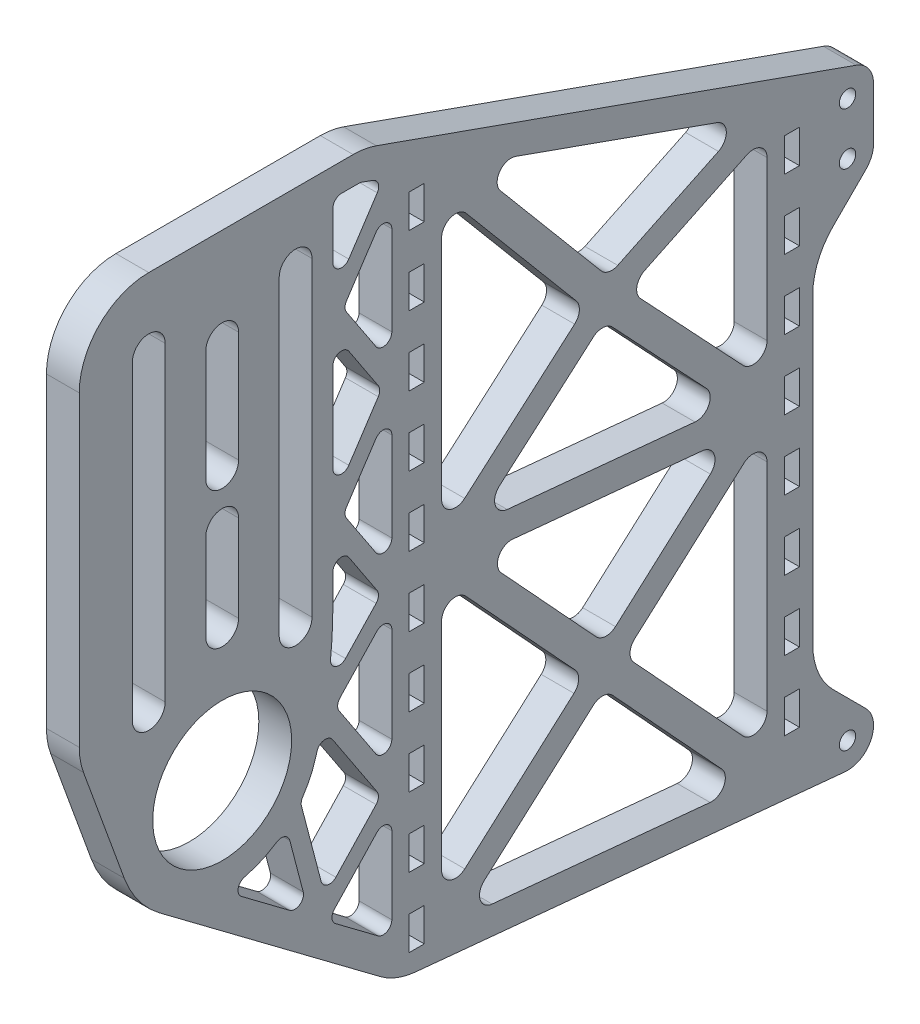
SolidWorks part; units mm, degrees
ref_plane "Front Plane" through (0, 0, 0) normal (0, 0, 1) x (1, 0, 0)
ref_plane "Top Plane" through (0, 0, 0) normal (0, 1, 0) x (1, 0, 0)
ref_plane "Right Plane" through (0, 0, 0) normal (1, 0, 0) x (0, 0, -1)
sketch "PlateGeometry" plane through (0, 0, 0) normal (1, 0, 0) x (0, 0, -1)
  line L1 (-38.1, -76.2) -> (38.1, -76.2) construction
  line L2 (-38.1, -76.2) -> (-38.1, 76.2) construction
  line L3 (-38.1, 76.2) -> (38.1, 76.2) construction
  line L4 (38.1, -76.2) -> (38.1, 76.2) construction
  line L5 (-38.1, -76.2) -> (38.1, 76.2) construction
  line L6 (-38.1, 76.2) -> (38.1, -76.2) construction
  line L11 (31.75, 76.2) -> (-31.75, 76.2) construction
  line L12 (31.75, 76.2) -> (31.75, -76.2) construction
  line L13 (31.75, -76.2) -> (-31.75, -76.2) construction
  line L14 (-31.75, 76.2) -> (-31.75, -76.2) construction
  line L15 (31.75, 76.2) -> (-31.75, -76.2) construction
  line L16 (31.75, -76.2) -> (-31.75, 76.2) construction
  point P0 (0, 0)
  point P9 (0, 0)
  line B0 (-35.7923, -66.6761) -> (-32.7923, -66.6739)
  line B1 (-35.7923, -66.6761) -> (-35.7877, -73.0261)
  line B2 (-35.7877, -73.0261) -> (-32.7877, -73.0239)
  line B3 (-32.7923, -66.6739) -> (-32.7877, -73.0239)
  line B4 (-35.7923, -66.6761) -> (-32.7877, -73.0239) construction
  line B5 (-35.7877, -73.0261) -> (-32.7923, -66.6739) construction
  line B6 (-35.7923, -53.9761) -> (-32.7923, -53.9739)
  line B7 (-35.7923, -53.9761) -> (-35.7877, -60.3261)
  line B8 (-35.7877, -60.3261) -> (-32.7877, -60.3239)
  line B9 (-32.7923, -53.9739) -> (-32.7877, -60.3239)
  line B10 (-35.7923, -53.9761) -> (-32.7877, -60.3239) construction
  line B11 (-35.7877, -60.3261) -> (-32.7923, -53.9739) construction
  line B12 (-35.7923, -41.2761) -> (-32.7923, -41.2739)
  line B13 (-35.7923, -41.2761) -> (-35.7877, -47.6261)
  line B14 (-35.7877, -47.6261) -> (-32.7877, -47.6239)
  line B15 (-32.7923, -41.2739) -> (-32.7877, -47.6239)
  line B16 (-35.7923, -41.2761) -> (-32.7877, -47.6239) construction
  line B17 (-35.7877, -47.6261) -> (-32.7923, -41.2739) construction
  line B18 (-35.7877, -34.9261) -> (-32.7877, -34.9239)
  line B19 (-32.7923, -28.5739) -> (-32.7877, -34.9239)
  line B20 (-35.7923, -15.8761) -> (-35.7877, -22.2261)
  line B21 (-35.7877, -22.2261) -> (-32.7877, -22.2239)
  line B22 (-32.7923, -15.8739) -> (-32.7877, -22.2239)
  line B23 (-35.7923, 9.5239) -> (-32.7923, 9.5261)
  line B24 (-32.7923, 9.5261) -> (-32.7877, 3.1761)
  line B25 (-35.7923, 9.5239) -> (-32.7877, 3.1761) construction
  line B26 (-35.7923, 22.2239) -> (-35.7877, 15.8739)
  line B27 (-35.7923, 34.9239) -> (-35.7877, 28.5739)
  line B28 (-35.7923, 47.6239) -> (-35.7877, 41.2739)
  line B29 (-35.7877, 41.2739) -> (-32.7923, 47.6261) construction
  line B30 (32.7886, -66.6757) -> (32.7914, -73.0257)
  line B31 (32.7914, -73.0257) -> (35.7914, -73.0243)
  line B32 (35.7886, -66.6743) -> (35.7914, -73.0243)
  line B33 (32.7886, -66.6757) -> (35.7914, -73.0243) construction
  line B34 (32.7914, -73.0257) -> (35.7886, -66.6743) construction
  line B35 (32.7886, -53.9757) -> (32.7914, -60.3257)
  line B36 (32.7914, -60.3257) -> (35.7914, -60.3243)
  line B37 (35.7886, -53.9743) -> (35.7914, -60.3243)
  line B38 (32.7886, -53.9757) -> (35.7914, -60.3243) construction
  line B39 (32.7914, -60.3257) -> (35.7886, -53.9743) construction
  line B40 (35.7886, -41.2743) -> (35.7914, -47.6243)
  line B41 (32.7914, -34.9257) -> (35.7914, -34.9243)
  line B42 (32.7886, -28.5757) -> (35.7914, -34.9243) construction
  line B43 (32.7886, -15.8757) -> (32.7914, -22.2257)
  line B44 (32.7886, -3.1757) -> (35.7914, -9.5243) construction
  line B45 (32.7914, -9.5257) -> (35.7886, -3.1743) construction
  line B46 (32.7886, 9.5243) -> (35.7886, 9.5257)
  line B47 (32.7886, 9.5243) -> (32.7914, 3.1743)
  line B48 (32.7914, 3.1743) -> (35.7914, 3.1757)
  line B49 (32.7886, 9.5243) -> (35.7914, 3.1757) construction
  line B50 (32.7886, 22.2243) -> (32.7914, 15.8743)
  line B51 (35.7886, 22.2257) -> (35.7914, 15.8757)
  line B52 (32.7886, 22.2243) -> (35.7914, 15.8757) construction
  line B53 (32.7914, 15.8743) -> (35.7886, 22.2257) construction
  line B54 (32.7914, 41.2743) -> (35.7914, 41.2757)
  line B55 (35.7886, 47.6257) -> (35.7914, 41.2757)
  line B56 (32.7886, 60.3243) -> (32.7914, 53.9743)
  line B57 (35.7886, 60.3257) -> (35.7914, 53.9757)
  line B58 (32.7886, 73.0243) -> (32.7914, 66.6743)
  line B59 (35.7886, 73.0257) -> (35.7914, 66.6757)
  line B60 (32.7914, 66.6743) -> (35.7886, 73.0257) construction
  circle B61 centre (-37.3063, -73.025) radius 5.5563 construction
  circle B62 centre (-37.3063, -73.025) radius 6.8263 construction
  circle B63 centre (-44.9262, -53.975) radius 5.5563 construction
  circle B64 centre (-44.9262, -53.975) radius 6.8263 construction
  dimension "D11" = 63.5
  dimension "D12" = 3.175
  dimension "D1" = 76.2
  dimension "D2" = 152.4
  dimension "D4" = 3.81
  dimension "D5" = 6.35
  dimension "D6" = 12.7
  dimension "D7" = 6.35
  dimension "D8" = 3.81
  dimension "D10" = 12.7
  dimension "D13" = 19.05
  dimension "D14" = 7.62
  dimension "D3" = 12
  dimension "D9" = 12
sketch_block_instance "SlotOutline-1"
sketch_block "SlotOutline" parameters "D1"=18.06, "D2"=7.2935
sketch_block_instance "SlotOutline-2"
sketch_block_instance "SlotOutline-3"
sketch_block_instance "SlotOutline-4"
sketch_block_instance "SlotOutline-5"
sketch_block_instance "SlotOutline-6"
sketch_block_instance "SlotOutline-7"
sketch_block_instance "SlotOutline-8"
sketch_block_instance "SlotOutline-9"
sketch_block_instance "SlotOutline-10"
sketch_block_instance "SlotOutline-11"
sketch_block_instance "SlotOutline-12"
sketch_block_instance "SlotOutline-13"
sketch_block_instance "SlotOutline-14"
sketch_block_instance "SlotOutline-15"
sketch_block_instance "SlotOutline-16"
sketch_block_instance "SlotOutline-17"
sketch_block_instance "SlotOutline-18"
sketch_block_instance "SlotOutline-19"
sketch_block_instance "SlotOutline-20"
sketch_block_instance "SlotOutline-21"
sketch_block_instance "SlotOutline-22"
sketch_block_instance "SlotOutline-23"
sketch_block_instance "SlotOutline-24"
sketch_block_instance "PulleyOutline-1"
sketch_block "PulleyOutline" parameters "D1"=11.1125, "D2"=13.6525
sketch_block_instance "PulleyOutline-2"
sketch "MotorGeometry" plane through (0, 0, 0) normal (1, 0, 0) x (0, 0, -1)
  line L0 (-83.2734, 1.775) -> (-83.2734, 49.025) construction
  line L3 (-50.2786, -55.4665) -> (-63.8121, -13.9087) construction
  line L4 (-41.2645, -76.9242) -> (-75.3216, -19.0975) construction
  line L5 (-38.1, -76.2) -> (-38.1, 76.2) construction
  line L6 (-38.1, -76.2) -> (38.1, -76.2) construction
  line L7 (38.1, -76.2) -> (38.1, 76.2) construction
  line L8 (-83.2734, 17.65) -> (-69.85, 9.9) construction
  line L9 (-69.85, 9.9) -> (-56.4266, 17.65) construction
  line L10 (-56.4266, 17.65) -> (-56.4266, 33.15) construction
  line L11 (-56.4266, 33.15) -> (-69.85, 40.9) construction
  line L12 (-69.85, 40.9) -> (-83.2734, 33.15) construction
  line L13 (-83.2734, 33.15) -> (-83.2734, 17.65) construction
  line L14 (-86.2734, 1.775) -> (-86.2734, 49.025)
  line L15 (-80.2734, 1.775) -> (-80.2734, 49.025)
  line L16 (-56.4266, 1.775) -> (-56.4266, 49.025) construction
  line L17 (-59.4266, 1.775) -> (-59.4266, 49.025)
  line L18 (-53.4266, 1.775) -> (-53.4266, 49.025)
  line L19 (-69.85, 8.3125) -> (-69.85, 47.25) construction
  line L20 (-72.85, 8.3125) -> (-72.85, 47.25)
  line L21 (-66.85, 8.3125) -> (-66.85, 47.25)
  circle A0 centre (44.45, -66.675) radius 1.5
  circle A1 centre (-69.85, -15.875) radius 11
  circle A5 centre (-69.85, -15.875) radius 30 construction
  circle A6 centre (-69.85, -15.875) radius 6.35 construction
  circle A7 centre (-44.9262, -53.975) radius 5.5562 construction
  circle A8 centre (-37.3063, -73.025) radius 5.5562 construction
  circle A9 centre (-69.85, -15.875) radius 25.5 construction
  circle A10 centre (-69.85, 25.4) radius 16 construction
  circle A11 centre (-69.85, 25.4) radius 11.5 construction
  circle A12 centre (-69.85, 25.4) radius 13.4234 construction
  arc A13 (-86.2734, 1.775) -> (-80.2734, 1.775) centre (-83.2734, 1.775) ccw
  arc A14 (-80.2734, 49.025) -> (-86.2734, 49.025) centre (-83.2734, 49.025) ccw
  arc A15 (-59.4266, 1.775) -> (-53.4266, 1.775) centre (-56.4266, 1.775) ccw
  arc A16 (-53.4266, 49.025) -> (-59.4266, 49.025) centre (-56.4266, 49.025) ccw
  arc A17 (-72.85, 8.3125) -> (-66.85, 8.3125) centre (-69.85, 8.3125) ccw
  arc A18 (-66.85, 47.25) -> (-72.85, 47.25) centre (-69.85, 47.25) ccw
  point P29 (-83.2734, 25.4)
  point P39 (-56.4266, 25.4)
  point P46 (-69.85, 27.7812)
  dimension "D1" = 22
  dimension "D4" = 60
  dimension "D5" = 12.7
  dimension "D7" = 4.5
  dimension "D8" = 32
  dimension "D9" = 4.5
  dimension "D13" = 3
  dimension "D3" = 6
  dimension "D2" = 31
  dimension "D6" = 38.1
  dimension "D10" = 31.75
  dimension "D11" = 9.525
  dimension "D12" = 6.35
  dimension "D14" = 15.875
  dimension "D15" = 1.5875
  dimension "D16" = 15.875
  dimension "D17" = 6.35
  dimension "D18" = 41.275
sketch "Sketch4" plane through (0, 0, 0) normal (1, 0, 0) x (0, 0, -1)
  line L0 (49.2125, 25.4) -> (49.2125, 34.925)
  line L1 (47.8176, 22.0324) -> (38.1, 12.3148)
  line L2 (-30.48, -50.8) -> (-38.1, -50.8) construction
  line L3 (-30.48, -50.8) -> (-30.48, -63.5) construction
  line L4 (-30.48, -63.5) -> (-38.1, -63.5) construction
  line L5 (-38.1, -50.8) -> (-38.1, -63.5) construction
  line L6 (-30.48, -50.8) -> (-38.1, -63.5) construction
  line L7 (-30.48, -63.5) -> (-38.1, -50.8) construction
  line L8 (38.1, 12.3148) -> (38.1, -53.5898)
  line L9 (38.1, -53.5898) -> (47.8176, -63.3074)
  line L10 (38.1, -76.2) -> (38.1, 76.2) construction
  line L11 (43.9929, -71.4155) -> (-38.1, -63.5)
  line L12 (-38.1, -63.5) -> (-81.28, -31.115)
  line L13 (-87.7511, -22.3905) -> (-95.9734, 0.2)
  line L14 (-95.9734, 0.2) -> (-95.9734, 71.25)
  line L15 (-43.7266, 71.25) -> (46.0419, 39.4136)
  line L16 (-95.9734, 71.25) -> (-43.7266, 71.25)
  line L17 (-83.2734, 1.775) -> (-83.2734, 58.55) construction
  line L18 (-86.2734, 1.775) -> (-86.2734, 58.55)
  line L19 (-80.2734, 1.775) -> (-80.2734, 58.55)
  line L20 (-69.85, 8.3125) -> (-69.85, 53.6) construction
  line L21 (-72.85, 8.3125) -> (-72.85, 53.6)
  line L22 (-66.85, 8.3125) -> (-66.85, 53.6)
  line L23 (-56.4266, 1.775) -> (-56.4266, 58.55) construction
  line L24 (-59.4266, 1.775) -> (-59.4266, 58.55)
  line L25 (-53.4266, 1.775) -> (-53.4266, 58.55)
  circle A0 centre (44.45, 25.4) radius 1.5
  circle A1 centre (44.45, 34.925) radius 1.5
  circle A2 centre (44.45, -66.675) radius 4.7625 construction
  circle A3 centre (44.45, 25.4) radius 4.7625 construction
  circle A4 centre (44.45, 34.925) radius 4.7625 construction
  circle A5 centre (-69.85, -15.875) radius 12.7
  arc A6 (43.9929, -71.4155) -> (47.8176, -63.3074) centre (44.45, -66.675) ccw
  circle A7 centre (-69.85, -15.875) radius 19.05
  arc A8 (47.8176, 22.0324) -> (49.2125, 25.4) centre (44.45, 25.4) ccw
  arc A9 (49.2125, 34.925) -> (46.0419, 39.4136) centre (44.45, 34.925) ccw
  circle A10 centre (44.45, -66.675) radius 1.5
  arc A11 (-86.2734, 1.775) -> (-80.2734, 1.775) centre (-83.2734, 1.775) ccw
  arc A12 (-80.2734, 58.55) -> (-86.2734, 58.55) centre (-83.2734, 58.55) ccw
  arc A13 (-72.85, 8.3125) -> (-66.85, 8.3125) centre (-69.85, 8.3125) ccw
  arc A14 (-66.85, 53.6) -> (-72.85, 53.6) centre (-69.85, 53.6) ccw
  arc A15 (-59.4266, 1.775) -> (-53.4266, 1.775) centre (-56.4266, 1.775) ccw
  arc A16 (-53.4266, 58.55) -> (-59.4266, 58.55) centre (-56.4266, 58.55) ccw
  arc A17 (-72.85, 24.1875) -> (-66.85, 24.1875) centre (-69.85, 24.1875) cw
  arc A18 (-72.85, 33.3625) -> (-66.85, 33.3625) centre (-69.85, 33.3625) ccw
  point P12 (-34.29, -57.15)
  point P36 (-83.2734, 30.1625)
  point P47 (-69.85, 30.9562)
  point P55 (-56.4266, 30.1625)
  dimension "D1" = 3
  dimension "D4" = 9.525
  dimension "D9" = 25.4
  dimension "D10" = 38.1
  dimension "D11" = 6
  dimension "D14" = 3.175
  dimension "D2" = 9.525
  dimension "D3" = 101.6
  dimension "D5" = 3.81
  dimension "D6" = 12.7
  dimension "D7" = 45
  dimension "D8" = 45
  dimension "D12" = 12.7
  dimension "D13" = 25.4
  dimension "D15" = 15.875
  dimension "D16" = 12.7
  dimension "D17" = 12.7
  dimension "D18" = 20
  dimension "D19" = 12.7
extrude "Boss-Extrude1" add sketch "Sketch4" along normal mid plane 6 contours L0 A9 L13 A7 L12 L11 A6 L9 L8 L1 A8 A0 A1 | A7 A5 | A18 L21 A17 L22 region at (0, 1.9375, 18.512) region at (0, 2.355, 73.0644) region at (0, 28.775, 69.85)
sketch "Sketch5" plane through (3, 0, 0) normal (1, 0, 0) x (0, 0, -1)
  line B0 (35.665, -54.102) -> (32.915, -54.102)
  line B1 (35.665, -54.102) -> (35.665, -60.198)
  line B2 (35.665, -60.198) -> (32.915, -60.198)
  line B3 (32.915, -54.102) -> (32.915, -60.198)
  line B4 (35.665, -54.102) -> (32.915, -60.198) construction
  line B5 (35.665, -60.198) -> (32.915, -54.102) construction
  line B6 (-32.915, -54.102) -> (-35.665, -54.102)
  line B7 (-32.915, -54.102) -> (-32.915, -60.198)
  line B8 (-32.915, -60.198) -> (-35.665, -60.198)
  line B9 (-35.665, -54.102) -> (-35.665, -60.198)
  line B10 (-32.915, -54.102) -> (-35.665, -60.198) construction
  line B11 (-32.915, -60.198) -> (-35.665, -54.102) construction
sketch_block_instance "Slot-1"
sketch_block "Slot" parameters "D1"=11.2845, "D2"=5.6739
sketch_block_instance "Slot-2"
extrude "LowerSlot" cut sketch "Sketch5" against normal through all both and the other way through all contours B0 B3 B2 B1 region at (3, -57.15, -34.29)
extrude "UpperSlot" cut sketch "Sketch5<3>" against normal through all both and the other way through all contours B6 B9 B8 B7 region at (3, -57.15, 34.29)
sketch "Sketch5<3>" plane through (3, 0, 0) normal (1, 0, 0) x (0, 0, -1) same geometry as "Sketch5"
pattern_linear "LowerSlots" count 8 spacing 12.7 along (0, 1, 0) of "LowerSlot"
pattern_linear "LPattern2" count 10 spacing 12.7 along (0, 1, 0) of "UpperSlot"
sketch "Sketch6" plane through (3, 0, 0) normal (1, 0, 0) x (0, 0, -1)
  line L1 (-38.84, -56.595) -> (-38.84, 64.1269)
  line L2 (-49.6166, 1.775) -> (-49.6166, 58.55)
  line L3 (-49.6166, 1.775) -> (-49.6166, 58.55)
  line L4 (-29.74, 60.8996) -> (-29.74, -59.2025)
  line L5 (29.74, -64.9377) -> (29.74, 39.805)
  line L6 (32.915, -54.102) -> (32.915, -60.198) construction
  line L8 (-32.915, -54.102) -> (-32.915, -60.198) construction
  line L9 (-35.665, -54.102) -> (-35.665, -60.198) construction
  line L11 (-49.6166, 58.55) -> (-49.6166, 66.17)
  line L12 (29.74, -6.1471) -> (0, 25.5315) construction
  line L14 (29.74, -6.1471) -> (-29.74, -59.2025) construction
  line L15 (-29.74, -0.412) -> (29.74, -64.9377) construction
  line L16 (0, 25.5315) -> (-29.74, -0.412) construction
  line L17 (0, 25.5315) -> (-29.74, 60.8996) construction
  line L18 (0, 25.5315) -> (29.74, 39.805) construction
  line L19 (0, -32.6748) -> (0, 25.5315) construction
  line L20 (44.1325, 25.5315) -> (44.1325, 34.7007)
  line L21 (44.1325, 34.7007) -> (-44.6007, 66.17)
  line L22 (-44.6007, 66.17) -> (-90.8934, 66.17)
  line L23 (-90.8934, 66.17) -> (-90.8934, 1.0957)
  line L24 (-90.8934, 1.0957) -> (-82.9775, -20.653)
  line L25 (-78.232, -27.051) -> (-36.1929, -58.5803)
  line L26 (-36.1929, -58.5803) -> (43.6001, -66.2741)
  line L27 (43.6001, -66.2741) -> (33.02, -55.694)
  line L28 (33.02, -55.694) -> (33.02, 14.419)
  line L29 (33.02, 14.419) -> (44.1325, 25.5315)
  line L30 (44.1325, 25.5315) -> (44.1325, 34.7007)
  line L31 (44.1325, 34.7007) -> (-44.6007, 66.17)
  line L32 (-44.6007, 66.17) -> (-90.8934, 66.17)
  line L33 (-90.8934, 66.17) -> (-90.8934, 1.0957)
  line L34 (-90.8934, 1.0957) -> (-82.9775, -20.653)
  line L35 (-78.232, -27.051) -> (-36.1929, -58.5803)
  line L36 (-36.1929, -58.5803) -> (43.6001, -66.2741)
  line L37 (43.6001, -66.2741) -> (33.02, -55.694)
  line L38 (33.02, -55.694) -> (33.02, 14.419)
  line L39 (33.02, 14.419) -> (44.1325, 25.5315)
  line L40 (-29.74, -0.412) -> (29.74, -6.1471) construction
  line L41 (28.0492, -4.2516) -> (-31.4308, -57.307)
  line L42 (-31.6076, -2.1335) -> (27.8724, -66.6592)
  line L43 (-29.9838, -2.9402) -> (29.4962, -8.6754)
  line L44 (-1.6697, 27.4456) -> (-31.4097, 1.5021)
  line L45 (31.5918, -4.4086) -> (1.8518, 27.27)
  line L46 (1.099, 23.2416) -> (30.839, 37.5151)
  line L47 (1.9441, 27.1662) -> (-27.7959, 62.5343)
  line L48 (31.4308, -8.0426) -> (-28.0492, -61.098)
  line L49 (-27.8724, 1.3096) -> (31.6076, -63.2161)
  line L50 (-29.4962, 2.1163) -> (29.9838, -3.6188)
  line L51 (1.6697, 23.6174) -> (-28.0703, -2.326)
  line L52 (27.8882, -7.8856) -> (-1.8518, 23.793)
  line L53 (-1.099, 27.8214) -> (28.641, 42.0949)
  line L54 (-1.9441, 23.8968) -> (-31.6841, 59.2649)
  line L55 (-38.84, 64.1269) -> (-49.6166, 47.8087) construction
  line L56 (-49.6166, 47.8087) -> (-38.84, 31.4904) construction
  line L57 (-38.84, 31.4904) -> (-49.6166, 15.1721) construction
  line L58 (-49.6166, 15.1721) -> (-38.84, -1.1462) construction
  line L59 (-38.84, -1.1462) -> (-51.1968, -14.2943) construction
  line L60 (-51.1968, -14.2943) -> (-38.84, -33.0054) construction
  line L61 (-38.84, -33.0054) -> (-51.844, -46.842) construction
  line L62 (-51.844, -46.842) -> (-56.7923, -27.9425) construction
  line L63 (-49.6166, 47.8087) -> (-38.84, 47.8087) construction
  line L64 (-40.1647, 65.0018) -> (-51.519, 47.8087)
  line L65 (-51.519, 47.8087) -> (-40.7424, 31.4904)
  line L66 (-40.7424, 31.4904) -> (-51.519, 15.1721)
  line L67 (-51.519, 15.1721) -> (-40.8564, -0.9736)
  line L68 (-40.8564, -0.9736) -> (-53.2132, -14.1217)
  line L69 (-53.2132, -14.1217) -> (-40.8564, -32.8328)
  line L70 (-40.8564, -32.8328) -> (-51.0352, -43.6634)
  line L71 (-51.0352, -43.6634) -> (-55.8417, -25.3054)
  line L72 (-37.5153, 63.2521) -> (-47.7142, 47.8087)
  line L73 (-47.7142, 47.8087) -> (-36.9376, 31.4904)
  line L74 (-36.9376, 31.4904) -> (-47.7142, 15.1721)
  line L75 (-47.7142, 15.1721) -> (-36.8236, -1.3187)
  line L76 (-36.8236, -1.3187) -> (-49.1804, -14.4668)
  line L77 (-49.1804, -14.4668) -> (-36.8236, -33.1779)
  line L78 (-36.8236, -33.1779) -> (-52.6527, -50.0207)
  line L79 (-52.6527, -50.0207) -> (-58.328, -28.3446)
  line L80 (-51.0352, -43.6634) -> (-55.2566, -27.5404) construction
  arc A0 (-49.6166, 1.775) -> (-52.7441, -20.7242) centre (-132.1114, 1.775) cw
  circle A6 centre (-69.85, -15.875) radius 17.78
  circle A7 centre (-69.85, -15.875) radius 17.78
  arc A8 (-82.9775, -20.653) -> (-78.232, -27.051) centre (-69.85, -15.875) ccw
  arc A9 (-82.9775, -20.653) -> (-78.232, -27.051) centre (-69.85, -15.875) ccw
  dimension "D4" = 3.175
  dimension "D5" = 3.175
  dimension "D6" = 3.175
  dimension "D9" = 3.175
  dimension "D1" = 5.08
  dimension "D2" = 5.08
  dimension "D3" = 3.81
  dimension "D7" = 2.54
  dimension "D8" = 2.54
extrude "Cut-Extrude1" cut sketch "Sketch6" against normal through all both and the other way through all contours L42 L4 L41 | L42 L48 L36 | L48 L49 L5 | L43 L49 L41 | L50 L52 L51 | L46 L45 L5 | L47 L53 L31 | L44 L54 L4 region at (3, -30.8188, 21.0325) region at (3, -53.4468, 0.174) region at (3, -13.6041, -0.174) region at (3, -34.5308, -21.0325) region at (3, 28.5725, 21.0098) region at (3, 6.862, 0.1757) region at (3, 19.7645, -21.2351) region at (3, 42.9661, -0.6765)
extrude "Cut-Extrude2" cut sketch "Sketch6<3>" against normal through all both and the other way through all contours A7 L35 L79 | L1 L78 L35 | A7 L71 L70 L69 A0 | L76 L77 L1 | L3 A0 L68 L67 | L74 L75 L1 | L66 L65 L3 | L72 L73 L1 | L64 L31 L32 L11 L3 region at (3, -46.5729, 42.7487) region at (3, -16.0186, 42.2868) region at (3, -36.4632, 60.1732) region at (3, 15.1721, 41.7981) region at (3, -30.5698, 49.1442) region at (3, 47.8087, 41.7981) region at (3, 0.0237, 46.8241) region at (3, 60.7684, 46.4548) region at (3, 31.4904, 46.6586)
sketch "Sketch6<3>" plane through (3, 0, 0) normal (1, 0, 0) x (0, 0, -1) same geometry as "Sketch6"
fillet "Fillet1" radius 2.54 24 edges at (0, 25.8059, 3.5493) (0, 56.953, 29.74) (0, 2.9587, 29.74) (0, 28.6736, -0.6765) (0, 41.0022, -26.3642) (0, 59.2225, 25.0112) (0, 24.742, -4.2252) (0, -2.4361, -29.74) (0, 36.9876, -29.74) (0, -2.972, -23.2753) (0, 22.0076, 0.1757) (0, 1.5504, 23.6266) (0, -29.116, -0.174) (0, -8.1179, -23.7147) (0, -32.8517, -3.6175) (0, -61.1901, -29.74) (0, -9.5507, -29.74) (0, -36.2336, 0.174) (0, -59.5346, 26.2964) (0, -64.5721, -25.9485) (0, -4.1595, 29.74) (0, -55.7989, 29.74) (0, -32.498, 3.6175) (0, -3.5782, 23.3668)
fillet "Fillet2" radius 1.5875 29 edges at (0, 64.6736, 40.3814) (0, 66.17, 49.6166) (0, 50.6894, 49.6166) (0, 47.8087, 47.7142) (0, 34.3711, 38.84) (0, 61.2462, 38.84) (0, 31.4904, 40.7424) (0, 44.9279, 49.6166) (0, 18.0528, 49.6166) (0, 15.1721, 47.7142) (0, 1.7346, 38.84) (0, 28.6097, 38.84) (0, -11.426, 50.6797) (0, -0.9736, 40.8564) (0, 12.2914, 49.6166) (0, -30.1246, 38.84) (0, -3.4642, 38.84) (0, -43.6634, 51.0352) (0, -32.8328, 40.8564) (0, -35.3234, 38.84) (0, -47.8004, 50.5661) (0, -56.595, 38.84) (0, -33.6501, 69.4332) (0, -45.3105, 53.886) (0, -29.2185, 58.0992) (0, -14.4668, 49.1804)
fillet "Fillet3" radius 12.7 6 edges at (0, -63.5, 38.1) (0, 71.25, 43.7266) (0, 71.25, 95.9734) (0, 0.2, 95.9734) (0, 12.3148, -38.1) (0, -53.5898, -38.1)
